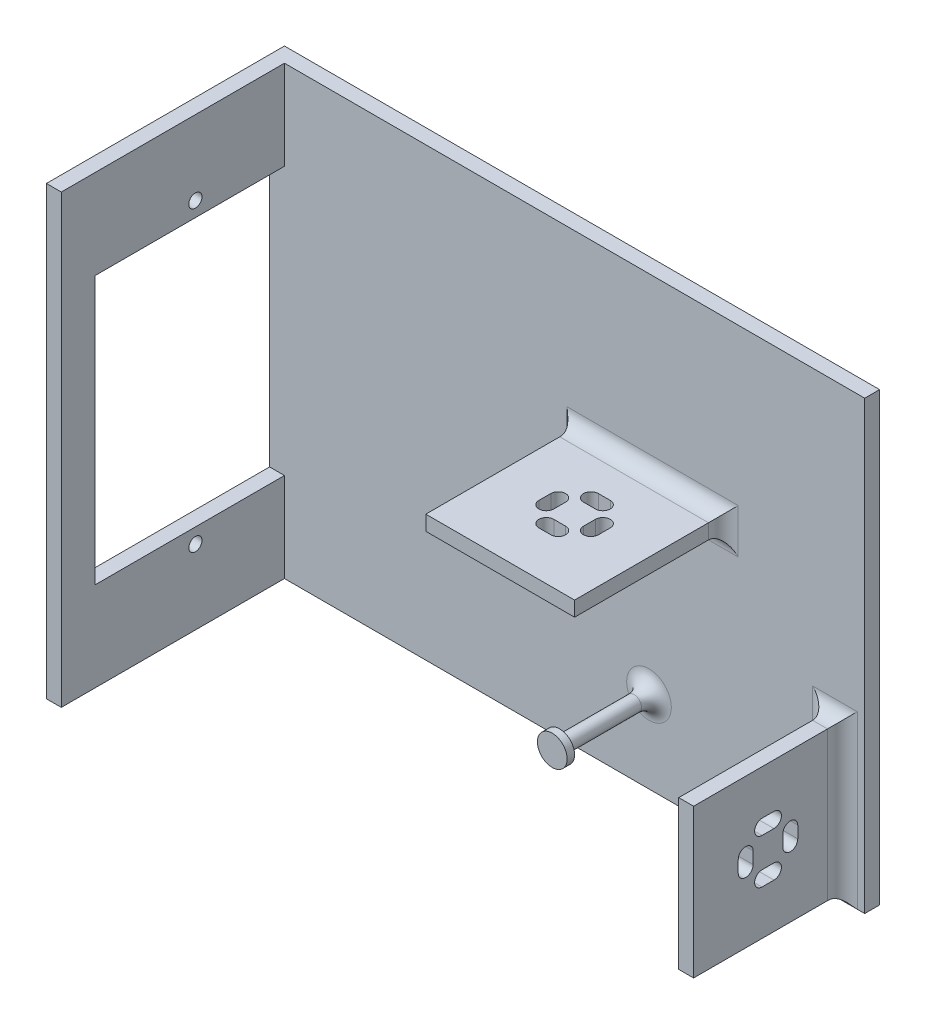
SolidWorks part; units mm, degrees
ref_plane "Front Plane" through (0, 0, 0) normal (0, 0, 1) x (1, 0, 0)
ref_plane "Top Plane" through (0, 0, 0) normal (0, 1, 0) x (1, 0, 0)
ref_plane "Right Plane" through (0, 0, 0) normal (1, 0, 0) x (0, 0, -1)
sketch "Sketch1" plane through (0, 0, 0) normal (0, 0, 1) x (1, 0, 0)
  line L1 (-25.4, -25.4) -> (25.4, -25.4)
  line L2 (-25.4, -25.4) -> (-25.4, 25.4)
  line L3 (-25.4, 25.4) -> (25.4, 25.4)
  line L4 (25.4, -25.4) -> (25.4, 25.4)
  line L5 (-25.4, -25.4) -> (25.4, 25.4) construction
  line L6 (-25.4, 25.4) -> (25.4, -25.4) construction
  point P0 (0, 0)
  dimension "D1" = 50.8
  dimension "D2" = 50.8
extrude "base" add sketch "Sketch1" along normal blind 2.54
sketch "Sketch2" plane through (0, 0, 2.54) normal (0, 0, 1) x (1, 0, 0)
  circle A0 centre (-11.43, -11.43) radius 1.27
  dimension "D1" = 2.54
extrude "post for wing" add sketch "Sketch2" along normal blind 15.24
sketch "Sketch4" plane through (0, 0, 2.54) normal (0, 0, 1) x (1, 0, 0)
  line L1 (-24.13, 19.05) -> (1.27, 19.05)
  line L2 (-24.13, 19.05) -> (-24.13, 21.59)
  line L3 (-24.13, 21.59) -> (1.27, 21.59)
  line L4 (1.27, 19.05) -> (1.27, 21.59)
  line L5 (-24.13, 19.05) -> (1.27, 21.59) construction
  line L6 (-24.13, 21.59) -> (1.27, 19.05) construction
  point P0 (-11.43, 20.32)
  dimension "D1" = 2.54
  dimension "D2" = 25.4
extrude "button holder" add sketch "Sketch4" along normal blind 25.4
ref_point "centre of button"
ref_axis "button axis" through (-11.43, 21.59, 15.24) along (0, 1, 0)
sketch "Sketch6" plane through (0, 21.59, 0) normal (0, 1, 0) x (1, 0, 0)
  line L0 (-12.446, -19.05) -> (-10.414, -19.05) construction
  line L1 (-12.446, -17.78) -> (-10.414, -17.78)
  line L2 (-12.446, -20.32) -> (-10.414, -20.32)
  arc A0 (-12.446, -17.78) -> (-12.446, -20.32) centre (-12.446, -19.05) ccw
  arc A1 (-10.414, -20.32) -> (-10.414, -17.78) centre (-10.414, -19.05) ccw
  point P2 (-11.43, -19.05)
  dimension "D2" = 1.27
  dimension "D1" = 2.032
  dimension "D3" = 0
  dimension "D4" = 3.81
extrude "one button leg hole" cut sketch "Sketch6" against normal blind 6.35
pattern_circular "moar leg holes" count 4 over 360 about axis through (-11.43, 21.59, 15.24) along (0, 1, 0) of "one button leg hole"
fillet "make everything not break" radius 2.54 4 edges at (1.27, 20.32, 2.54) (-11.43, 19.05, 2.54) (-11.43, 21.59, 2.54) (-24.13, 20.32, 2.54)
ref_axis "rotate for second button" through (-11.43, -11.43, 17.78) along (0, 0, -1)
pattern_circular "second button" count 2 every 90 about axis through (-11.43, -11.43, 17.78) along (0, 0, -1) of "button holder", "one button leg hole", "moar leg holes", "make everything not break"
sketch "Sketch3" plane through (0, 0, 17.78) normal (0, 0, 1) x (1, 0, 0)
  circle A0 centre (-11.43, -11.43) radius 2.54
  dimension "D1" = 5.08
extrude "don't let it fall off" add sketch "Sketch3" along normal blind 1.27
fillet "Fillet1" radius 2.54 1 edges at (-12.7, -11.43, 2.54)
sketch "Sketch7" plane through (0, 25.4, 0) normal (0, 1, 0) x (1, 0, 0)
  line L1 (-25.4, 0) -> (25.4, 0)
  line L2 (-25.4, 0) -> (-25.4, -2.54)
  line L3 (-25.4, -2.54) -> (25.4, -2.54)
  line L4 (25.4, 0) -> (25.4, -2.54)
extrude "awkward build 1" add sketch "Sketch7" along normal blind 25.4
sketch "Sketch8" plane through (-25.4, 0, 0) normal (-1, 0, 0) x (0, 0, 1)
  line L1 (0, 50.8) -> (2.54, 50.8)
  line L2 (0, 50.8) -> (0, -25.4)
  line L3 (0, -25.4) -> (2.54, -25.4)
  line L4 (2.54, 50.8) -> (2.54, -25.4)
extrude "awkward build 2" add sketch "Sketch8" along normal blind 50.8
sketch "Sketch9" plane through (0, 0, 2.54) normal (0, 0, 1) x (1, 0, 0)
  line L0 (-76.2, -25.4) -> (16.51, -25.4) construction
  line L1 (-76.2, 50.8) -> (-73.66, 50.8)
  line L2 (-76.2, 50.8) -> (-76.2, -25.4)
  line L3 (-76.2, -25.4) -> (-73.66, -25.4)
  line L4 (-73.66, 50.8) -> (-73.66, -25.4)
  dimension "D1" = 2.54
extrude "camera holder wall" add sketch "Sketch9" along normal blind 38.1
sketch "Sketch10" plane through (-76.2, 0, 0) normal (-1, 0, 0) x (0, 0, 1)
  line L0 (0, 50.8) -> (0, -25.4) construction
  line L1 (2.54, -10.16) -> (34.8488, -10.16)
  line L2 (2.54, -10.16) -> (2.54, 35.56)
  line L3 (2.54, 35.56) -> (34.8488, 35.56)
  line L4 (34.8488, -10.16) -> (34.8488, 35.56)
  line L5 (2.54, -10.16) -> (34.8488, 35.56) construction
  line L6 (2.54, 35.56) -> (34.8488, -10.16) construction
  line L7 (40.64, 50.8) -> (0, 50.8) construction
  point P0 (18.6944, 12.7)
  dimension "D1" = 2.54
  dimension "D2" = 45.72
  dimension "D3" = 38.1
  dimension "D4" = 32.3088
extrude "camera hole" cut sketch "Sketch10" against normal up to next
hole_wizard "camera mount holes" positions "Sketch12" profile "Sketch11" tap size "#4-40" standard "ANSI Inch" end condition up to next
sketch "Sketch12" plane through (-76.2, 0, 0) normal (-1, 0, 0) x (0, 0, 1)
  line L0 (0, 50.8) -> (0, -25.4) construction
  point P0 (17.7489, 38.1)
  point P2 (17.7489, -12.7)
  point P8 (0, 12.7)
  dimension "D1" = 50.8
  dimension "D2" = 25.4
sketch "Sketch11" plane through (-76.2, 38.1, 17.7489) normal (0, 1, 0) x (0, 0, 1)
  line L0 (0, 0) -> (0, 2.54)
  line L1 (0, 2.54) -> (1.1303, 2.54)
  line L2 (1.1303, 2.54) -> (1.1303, 0)
  line L5 (1.1303, 0) -> (0, 0)
  line L11 (0, -6.35) -> (0, 107.95) construction
  dimension "Thru Tap Drill Dia." = 2.2606
  dimension "Thru Tap Drill Depth" = 2.54
cosmetic thread "Hole Thread1"
cosmetic thread "Hole Thread2"
